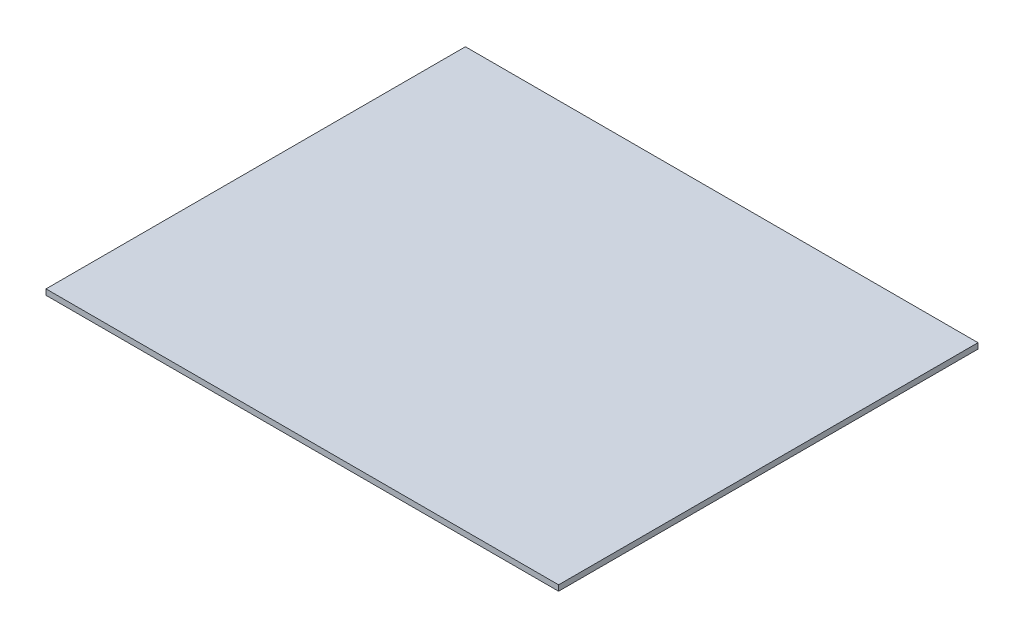
SolidWorks part; units mm, degrees
ref_plane "Front Plane" through (0, 0, 0) normal (0, 0, 1) x (1, 0, 0)
ref_plane "Top Plane" through (0, 0, 0) normal (0, 1, 0) x (1, 0, 0)
ref_plane "Right Plane" through (0, 0, 0) normal (1, 0, 0) x (0, 0, -1)
sketch "Sketch1" plane through (0, 0, 0) normal (0, 1, 0) x (1, 0, 0)
  line L1 (550, -450) -> (-550, -450)
  line L2 (550, -450) -> (550, 450)
  line L3 (550, 450) -> (-550, 450)
  line L4 (-550, -450) -> (-550, 450)
  line L5 (550, -450) -> (-550, 450) construction
  line L6 (550, 450) -> (-550, -450) construction
  point P0 (0, 0)
  dimension "D1" = 1100
  dimension "D2" = 900
extrude "Boss-Extrude1" add sketch "Sketch1" along normal mid plane 12
equation "\"M5_tap\"=4.2mm"
equation "\"M5_clearence\"=5.5mm"
equation "\"M6_tap\"=5mm"
equation "\"M6_clearence\"=6.6mm"
equation "\"work_area_width\"=1100mm"
equation "\"work_area_depth\"=900mm"
equation "\"D1@Sketch1\"=\"work_area_width\""
equation "\"D2@Sketch1\"=\"work_area_depth\""
